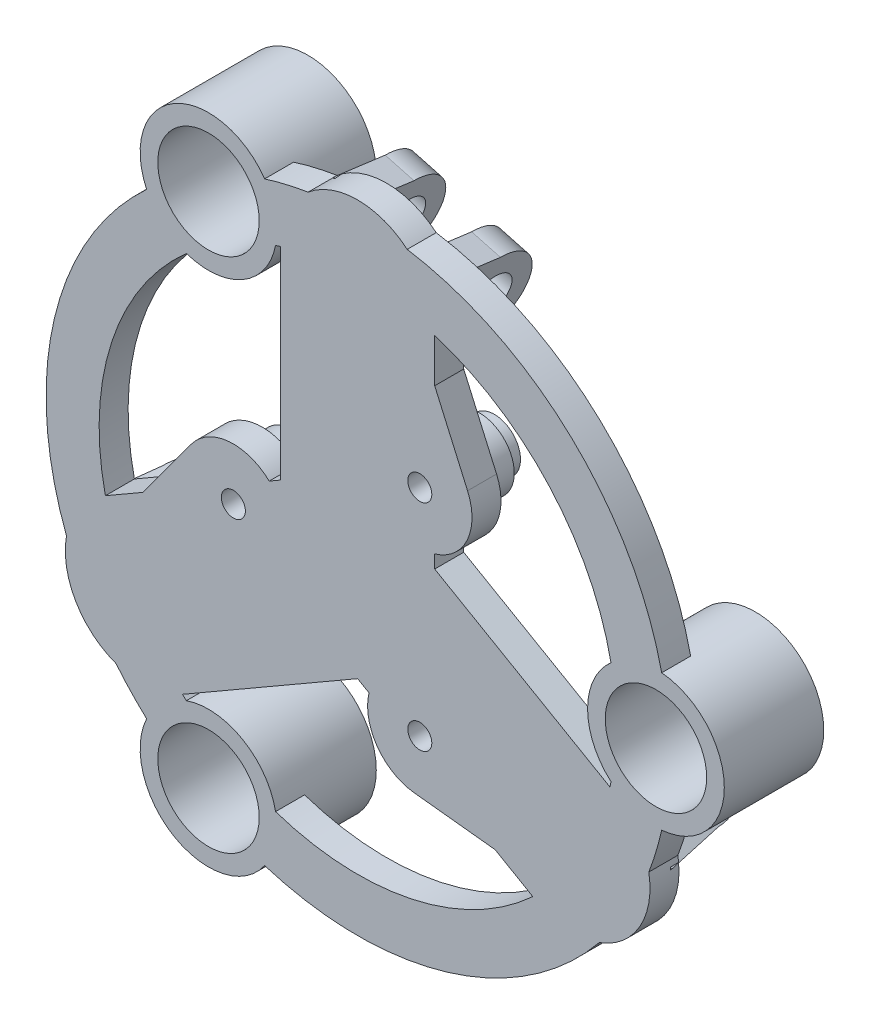
SolidWorks part; units mm, degrees
ref_plane "Front Plane" through (0, 0, 0) normal (0, 0, 1) x (1, 0, 0)
ref_plane "Top Plane" through (0, 0, 0) normal (0, 1, 0) x (1, 0, 0)
ref_plane "Right Plane" through (0, 0, 0) normal (1, 0, 0) x (0, 0, -1)
sketch "S01 - Joining centre of floating Y" plane through (0, 0, 0) normal (0, 0, 1) x (1, 0, 0)
  circle A0 centre (0, 0) radius 9
  dimension "D1" = 18
extrude "01 - Joining centre of floating Y" add sketch "S01 - Joining centre of floating Y" along normal blind 3.5 from offset 33.5
sketch "S02 - Floating spoke 1" plane through (0, 0, 0) normal (0, 0, 1) x (1, 0, 0)
  line L0 (4.65, -8.054) -> (-21.3308, -23.054)
  line L1 (-30.6308, -6.946) -> (-4.65, 8.054)
  arc A0 (-21.3308, -23.054) -> (-30.6308, -6.946) centre (-25.9808, -15) cw
  arc A1 (-4.65, 8.054) -> (4.65, -8.054) centre (0, 0) cw
  dimension "D1" = 9.3
  dimension "D2" = 9.3
  dimension "D3" = 4.65
  dimension "D4" = 4.65
  dimension "D5" = 21.3308
  dimension "D6" = 25.9808
  dimension "D7" = 30.6308
  dimension "D8" = 6.946
extrude "02 - Floating spoke 1" add sketch "S02 - Floating spoke 1" along normal blind 3.5 from offset 33.5
sketch "S03 - Floating spoke 2" plane through (0, 0, 0) normal (0, 0, 1) x (1, 0, 0)
  line L0 (4.65, 8.054) -> (30.6308, -6.946)
  line L1 (21.3308, -23.054) -> (-4.65, -8.054)
  arc A0 (30.6308, -6.946) -> (21.3308, -23.054) centre (25.9808, -15) cw
  arc A1 (-4.65, -8.054) -> (4.65, 8.054) centre (0, 0) cw
  dimension "D1" = 9.3
  dimension "D2" = 9.3
  dimension "D3" = 4.65
  dimension "D4" = 21.3308
  dimension "D5" = 25.9808
  dimension "D6" = 30.6308
  dimension "D7" = 4.65
  dimension "D8" = 6.946
extrude "03 - Floating spoke 2" add sketch "S03 - Floating spoke 2" along normal blind 3.5 from offset 33.5
sketch "S04 - Floating spoke 3" plane through (0, 0, 0) normal (0, 0, 1) x (1, 0, 0)
  line L0 (-9.3, 0) -> (-9.3, 30)
  line L1 (9.3, 30) -> (9.3, 0)
  arc A0 (-9.3, 30) -> (9.3, 30) centre (0, 30) cw
  arc A1 (9.3, 0) -> (-9.3, 0) centre (0, 0) cw
  dimension "D1" = 9.3
  dimension "D2" = 30
extrude "04 - Floating spoke 3" add sketch "S04 - Floating spoke 3" along normal blind 3.5 from offset 33.5
sketch "S05 - Moving tendon tie web 1" plane through (0, 0, 0) normal (0, 0, 1) x (1, 0, 0)
  line L0 (25.2997, -21.2631) -> (6.8189, -19.2535)
  line L1 (8.1811, -6.7273) -> (26.6618, -8.7369)
  arc A0 (6.8189, -19.2535) -> (8.1811, -6.7273) centre (7.5, -12.9904) cw
  arc A1 (26.6618, -8.7369) -> (25.2997, -21.2631) centre (25.9808, -15) cw
  dimension "D1" = 6.3
  dimension "D2" = 6.3
  dimension "D3" = 6.8189
  dimension "D4" = 7.5
  dimension "D5" = 8.1811
  dimension "D6" = 25.2997
  dimension "D7" = 25.9808
  dimension "D8" = 26.6618
  dimension "D9" = 6.7273
  dimension "D10" = 8.7369
extrude "05 - Moving tendon tie web 1" add sketch "S05 - Moving tendon tie web 1" along normal blind 3.5 from offset 33.5
sketch "S06 - Tendon anchor base 1" plane through (0, 0, 0) normal (0, 0, 1) x (1, 0, 0)
  circle A0 centre (7.5, -12.9904) radius 4.2
  dimension "D1" = 8.4
  dimension "D2" = 7.5
  dimension "D3" = 12.9904
extrude "06 - Tendon anchor base 1" add sketch "S06 - Tendon anchor base 1" along normal blind 3.7 from offset 29.8
sketch "S07 - Tendon mouth 1" plane through (0, 0, 0) normal (0, 0, 1) x (1, 0, 0)
  circle A0 centre (7.5, -12.9904) radius 3.15
  dimension "D1" = 6.3
  dimension "D2" = 7.5
  dimension "D3" = 12.9904
extrude "07 - Tendon mouth 1" add sketch "S07 - Tendon mouth 1" along normal blind 1.8 from offset 28
sketch "S08 - Moving tendon tie web 2" plane through (0, 0, 0) normal (0, 0, 1) x (1, 0, 0)
  line L0 (5.7645, 32.5417) -> (13.2645, 15.5321)
  line L1 (1.7355, 10.4487) -> (-5.7645, 27.4583)
  arc A0 (13.2645, 15.5321) -> (1.7355, 10.4487) centre (7.5, 12.9904) cw
  arc A1 (-5.7645, 27.4583) -> (5.7645, 32.5417) centre (0, 30) cw
  dimension "D1" = 6.3
  dimension "D2" = 6.3
  dimension "D3" = 1.7355
  dimension "D4" = 5.7645
  dimension "D5" = 7.5
  dimension "D6" = 13.2645
  dimension "D7" = 5.7645
  dimension "D8" = 10.4487
  dimension "D9" = 27.4583
extrude "08 - Moving tendon tie web 2" add sketch "S08 - Moving tendon tie web 2" along normal blind 3.5 from offset 33.5
sketch "S09 - Tendon anchor base 2" plane through (0, 0, 0) normal (0, 0, 1) x (1, 0, 0)
  circle A0 centre (7.5, 12.9904) radius 4.2
  dimension "D1" = 8.4
  dimension "D2" = 7.5
  dimension "D3" = 12.9904
extrude "09 - Tendon anchor base 2" add sketch "S09 - Tendon anchor base 2" along normal blind 3.7 from offset 29.8
sketch "S10 - Tendon mouth 2" plane through (0, 0, 0) normal (0, 0, 1) x (1, 0, 0)
  circle A0 centre (7.5, 12.9904) radius 3.15
  dimension "D1" = 6.3
  dimension "D2" = 7.5
  dimension "D3" = 12.9904
extrude "10 - Tendon mouth 2" add sketch "S10 - Tendon mouth 2" along normal blind 1.8 from offset 28
sketch "S11 - Moving tendon tie web 3" plane through (0, 0, 0) normal (0, 0, 1) x (1, 0, 0)
  line L0 (-31.0642, -11.2786) -> (-20.0835, 3.7214)
  line L1 (-9.9165, -3.7214) -> (-20.8973, -18.7214)
  arc A0 (-20.0835, 3.7214) -> (-9.9165, -3.7214) centre (-15, 0) cw
  arc A1 (-20.8973, -18.7214) -> (-31.0642, -11.2786) centre (-25.9808, -15) cw
  dimension "D1" = 6.3
  dimension "D2" = 6.3
  dimension "D3" = 9.9165
  dimension "D4" = 15
  dimension "D5" = 20.0835
  dimension "D6" = 20.8973
  dimension "D7" = 25.9808
  dimension "D8" = 31.0642
  dimension "D9" = 11.2786
extrude "11 - Moving tendon tie web 3" add sketch "S11 - Moving tendon tie web 3" along normal blind 3.5 from offset 33.5
sketch "S12 - Tendon anchor base 3" plane through (0, 0, 0) normal (0, 0, 1) x (1, 0, 0)
  circle A0 centre (-15, 0) radius 4.2
  dimension "D1" = 8.4
  dimension "D2" = 15
extrude "12 - Tendon anchor base 3" add sketch "S12 - Tendon anchor base 3" along normal blind 3.7 from offset 29.8
sketch "S13 - Tendon mouth 3" plane through (0, 0, 0) normal (0, 0, 1) x (1, 0, 0)
  circle A0 centre (-15, 0) radius 3.15
  dimension "D1" = 6.3
  dimension "D2" = 15
extrude "13 - Tendon mouth 3" add sketch "S13 - Tendon mouth 3" along normal blind 1.8 from offset 28
sketch "S14 - Joined drive hoop" plane through (0, 0, 0) normal (0, 0, 1) x (1, 0, 0)
  circle A0 centre (0, 0) radius 37.6
  circle A1 centre (0, 0) radius 31.2
  dimension "D1" = 62.4
  dimension "D2" = 75.2
extrude "14 - Joined drive hoop" add sketch "S14 - Joined drive hoop" along normal blind 3.5 from offset 33.5
sketch "S15 - Sliding guide barrel 1" plane through (0, 0, 0) normal (0, 0, 1) x (1, 0, 0)
  circle A0 centre (36, 0) radius 8.25
  dimension "D1" = 16.5
  dimension "D2" = 36
extrude "15 - Sliding guide barrel 1" add sketch "S15 - Sliding guide barrel 1" along normal blind 12 from offset 25
sketch "S16 - Sliding guide barrel 2" plane through (0, 0, 0) normal (0, 0, 1) x (1, 0, 0)
  circle A0 centre (-18, 31.1769) radius 8.25
  dimension "D1" = 16.5
  dimension "D2" = 18
  dimension "D3" = 31.1769
extrude "16 - Sliding guide barrel 2" add sketch "S16 - Sliding guide barrel 2" along normal blind 12 from offset 25
sketch "S17 - Sliding guide barrel 3" plane through (0, 0, 0) normal (0, 0, 1) x (1, 0, 0)
  circle A0 centre (-18, -31.1769) radius 8.25
  dimension "D1" = 16.5
  dimension "D2" = 18
  dimension "D3" = 31.1769
extrude "17 - Sliding guide barrel 3" add sketch "S17 - Sliding guide barrel 3" along normal blind 12 from offset 25
sketch "S18 - Guide bushing seats" plane through (0, 0, 0) normal (0, 0, 1) x (1, 0, 0)
  circle A0 centre (36, 0) radius 6.12
  circle A1 centre (-18, 31.1769) radius 6.12
  circle A2 centre (-18, -31.1769) radius 6.12
  dimension "D1" = 12.24
  dimension "D2" = 12.24
  dimension "D3" = 12.24
  dimension "D4" = 36
  dimension "D5" = 18
  dimension "D6" = 31.1769
  dimension "D7" = 31.1769
extrude "18 - Guide bushing seats" cut sketch "S18 - Guide bushing seats" along normal blind 14 from offset 24
sketch "S19 - Through tendon tie eyes" plane through (0, 0, 0) normal (0, 0, 1) x (1, 0, 0)
  circle A0 centre (7.5, -12.9904) radius 1.45
  circle A1 centre (7.5, 12.9904) radius 1.45
  circle A2 centre (-15, 0) radius 1.45
  dimension "D1" = 2.9
  dimension "D2" = 2.9
  dimension "D3" = 2.9
  dimension "D4" = 7.5
  dimension "D5" = 15
  dimension "D6" = 12.9904
  dimension "D7" = 12.9904
extrude "19 - Through tendon tie eyes" cut sketch "S19 - Through tendon tie eyes" along normal blind 10 from offset 27.8
sketch3d "Plane points - Integral B1 fork cheek L"
  point P0 (-25.9808, -15, 28)
  point P1 (-8.5941, -10.3413, 28)
  point P2 (-25.9808, -15, 10)
ref_plane "Drilling plane - Integral B1 fork cheek L" through (2.0096, -7.5, 0) normal (-0.2588, 0.9659, 0) x (0.9659, 0.2588, 0)
sketch "S20 - Integral B1 fork cheek L" plane through (2.0096, -7.5, 0) normal (-0.2588, 0.9659, 0) x (0.9659, 0.2588, 0)
  line L0 (-35.0778, -34.5) -> (-22.8778, -34.5)
  line L1 (-22.8778, -34.5) -> (-24.0278, -28)
  line L2 (-33.9278, -28) -> (-35.0778, -34.5)
  arc A0 (-24.0278, -28) -> (-33.9278, -28) centre (-28.9778, -28) ccw
  dimension "D1" = 4.95
  dimension "D2" = 22.8778
  dimension "D3" = 28.9778
  dimension "D4" = 35.0778
  dimension "D5" = 28
  dimension "D6" = 34.5
extrude "20 - Integral B1 fork cheek L" add sketch "S20 - Integral B1 fork cheek L" along normal blind 3.6 from offset 7.2 offset against normal yes
sketch3d "Plane points - Integral B1 fork cheek R"
  point P0 (-25.9808, -15, 28)
  point P1 (-8.5941, -10.3413, 28)
  point P2 (-25.9808, -15, 10)
ref_plane "Drilling plane - Integral B1 fork cheek R" through (2.0096, -7.5, 0) normal (-0.2588, 0.9659, 0) x (0.9659, 0.2588, 0)
sketch "S21 - Integral B1 fork cheek R" plane through (2.0096, -7.5, 0) normal (-0.2588, 0.9659, 0) x (0.9659, 0.2588, 0)
  line L0 (-35.0778, -34.5) -> (-22.8778, -34.5)
  line L1 (-22.8778, -34.5) -> (-24.0278, -28)
  line L2 (-33.9278, -28) -> (-35.0778, -34.5)
  arc A0 (-24.0278, -28) -> (-33.9278, -28) centre (-28.9778, -28) ccw
  dimension "D1" = 4.95
  dimension "D2" = 22.8778
  dimension "D3" = 28.9778
  dimension "D4" = 35.0778
  dimension "D5" = 28
  dimension "D6" = 34.5
extrude "21 - Integral B1 fork cheek R" add sketch "S21 - Integral B1 fork cheek R" along normal blind 3.6 from offset 3.6
sketch3d "Plane points - B1 pivot through both cheeks"
  point P0 (-25.9808, -15, 28)
  point P1 (-8.5941, -10.3413, 28)
  point P2 (-25.9808, -15, 10)
ref_plane "Drilling plane - B1 pivot through both cheeks" through (2.0096, -7.5, 0) normal (-0.2588, 0.9659, 0) x (0.9659, 0.2588, 0)
sketch "S22 - B1 pivot through both cheeks" plane through (2.0096, -7.5, 0) normal (-0.2588, 0.9659, 0) x (0.9659, 0.2588, 0)
  circle A0 centre (-28.9778, -28) radius 1.65
  dimension "D1" = 3.3
  dimension "D2" = 28.9778
  dimension "D3" = 28
extrude "22 - B1 pivot through both cheeks" cut sketch "S22 - B1 pivot through both cheeks" along normal blind 15 from offset 7.5 offset against normal yes
sketch3d "Plane points - B1 recessed pivot screw head"
  point P0 (-25.9808, -15, 28)
  point P1 (-8.5941, -10.3413, 28)
  point P2 (-25.9808, -15, 10)
ref_plane "Drilling plane - B1 recessed pivot screw head" through (2.0096, -7.5, 0) normal (-0.2588, 0.9659, 0) x (0.9659, 0.2588, 0)
sketch "S23 - B1 recessed pivot screw head" plane through (2.0096, -7.5, 0) normal (-0.2588, 0.9659, 0) x (0.9659, 0.2588, 0)
  circle A0 centre (-28.9778, -28) radius 2.7
  dimension "D1" = 5.4
  dimension "D2" = 28.9778
  dimension "D3" = 28
extrude "23 - B1 recessed pivot screw head" cut sketch "S23 - B1 recessed pivot screw head" along normal blind 1.5 from offset 7.3 offset against normal yes
sketch3d "Plane points - Integral B2 fork cheek L"
  point P0 (25.9808, -15, 28)
  point P1 (13.2528, -2.2721, 28)
  point P2 (25.9808, -15, 10)
ref_plane "Drilling plane - Integral B2 fork cheek L" through (5.4904, 5.4904, 0) normal (-0.7071, -0.7071, 0) x (0, 0, 1)
sketch "S24 - Integral B2 fork cheek L" plane through (5.4904, 5.4904, 0) normal (-0.7071, -0.7071, 0) x (0, 0, 1)
  line L0 (34.5, -35.0778) -> (34.5, -22.8778)
  line L1 (34.5, -22.8778) -> (28, -24.0278)
  line L2 (28, -33.9278) -> (34.5, -35.0778)
  arc A0 (28, -24.0278) -> (28, -33.9278) centre (28, -28.9778) ccw
  dimension "D1" = 4.95
  dimension "D2" = 28
  dimension "D3" = 34.5
  dimension "D4" = 22.8778
  dimension "D5" = 28.9778
  dimension "D6" = 35.0778
extrude "24 - Integral B2 fork cheek L" add sketch "S24 - Integral B2 fork cheek L" along normal blind 3.6 from offset 7.2 offset against normal yes
sketch3d "Plane points - Integral B2 fork cheek R"
  point P0 (25.9808, -15, 28)
  point P1 (13.2528, -2.2721, 28)
  point P2 (25.9808, -15, 10)
ref_plane "Drilling plane - Integral B2 fork cheek R" through (5.4904, 5.4904, 0) normal (-0.7071, -0.7071, 0) x (0, 0, 1)
sketch "S25 - Integral B2 fork cheek R" plane through (5.4904, 5.4904, 0) normal (-0.7071, -0.7071, 0) x (0, 0, 1)
  line L0 (34.5, -35.0778) -> (34.5, -22.8778)
  line L1 (34.5, -22.8778) -> (28, -24.0278)
  line L2 (28, -33.9278) -> (34.5, -35.0778)
  arc A0 (28, -24.0278) -> (28, -33.9278) centre (28, -28.9778) ccw
  dimension "D1" = 4.95
  dimension "D2" = 28
  dimension "D3" = 34.5
  dimension "D4" = 22.8778
  dimension "D5" = 28.9778
  dimension "D6" = 35.0778
extrude "25 - Integral B2 fork cheek R" add sketch "S25 - Integral B2 fork cheek R" along normal blind 3.6 from offset 3.6
sketch3d "Plane points - B2 pivot through both cheeks"
  point P0 (25.9808, -15, 28)
  point P1 (13.2528, -2.2721, 28)
  point P2 (25.9808, -15, 10)
ref_plane "Drilling plane - B2 pivot through both cheeks" through (5.4904, 5.4904, 0) normal (-0.7071, -0.7071, 0) x (0, 0, 1)
sketch "S26 - B2 pivot through both cheeks" plane through (5.4904, 5.4904, 0) normal (-0.7071, -0.7071, 0) x (0, 0, 1)
  circle A0 centre (28, -28.9778) radius 2.6
  dimension "D1" = 5.2
  dimension "D2" = 28
  dimension "D3" = 28.9778
extrude "26 - B2 pivot through both cheeks" cut sketch "S26 - B2 pivot through both cheeks" along normal blind 15 from offset 7.5 offset against normal yes
sketch3d "Plane points - B2 recessed pivot screw head"
  point P0 (25.9808, -15, 28)
  point P1 (13.2528, -2.2721, 28)
  point P2 (25.9808, -15, 10)
ref_plane "Drilling plane - B2 recessed pivot screw head" through (5.4904, 5.4904, 0) normal (-0.7071, -0.7071, 0) x (0, 0, 1)
sketch "S27 - B2 recessed pivot screw head" plane through (5.4904, 5.4904, 0) normal (-0.7071, -0.7071, 0) x (0, 0, 1)
  circle A0 centre (28, -28.9778) radius 2.7
  dimension "D1" = 5.4
  dimension "D2" = 28
  dimension "D3" = 28.9778
extrude "27 - B2 recessed pivot screw head" cut sketch "S27 - B2 recessed pivot screw head" along normal blind 1.5 from offset 7.3 offset against normal yes
sketch3d "Plane points - Integral B3 fork cheek L"
  point P0 (0, 30, 28)
  point P1 (-4.6587, 12.6133, 28)
  point P2 (0, 30, 10)
ref_plane "Drilling plane - Integral B3 fork cheek L" through (-7.5, 2.0096, 0) normal (0.9659, -0.2588, 0) x (0, 0, -1)
sketch "S28 - Integral B3 fork cheek L" plane through (-7.5, 2.0096, 0) normal (0.9659, -0.2588, 0) x (0, 0, -1)
  line L0 (-34.5, 35.0778) -> (-34.5, 22.8778)
  line L1 (-34.5, 22.8778) -> (-28, 24.0278)
  line L2 (-28, 33.9278) -> (-34.5, 35.0778)
  arc A0 (-28, 24.0278) -> (-28, 33.9278) centre (-28, 28.9778) ccw
  dimension "D1" = 4.95
  dimension "D2" = 28
  dimension "D3" = 34.5
  dimension "D4" = 22.8778
  dimension "D5" = 28.9778
  dimension "D6" = 35.0778
extrude "28 - Integral B3 fork cheek L" add sketch "S28 - Integral B3 fork cheek L" along normal blind 3.6 from offset 7.2 offset against normal yes
sketch3d "Plane points - Integral B3 fork cheek R"
  point P0 (0, 30, 28)
  point P1 (-4.6587, 12.6133, 28)
  point P2 (0, 30, 10)
ref_plane "Drilling plane - Integral B3 fork cheek R" through (-7.5, 2.0096, 0) normal (0.9659, -0.2588, 0) x (0, 0, -1)
sketch "S29 - Integral B3 fork cheek R" plane through (-7.5, 2.0096, 0) normal (0.9659, -0.2588, 0) x (0, 0, -1)
  line L0 (-34.5, 35.0778) -> (-34.5, 22.8778)
  line L1 (-34.5, 22.8778) -> (-28, 24.0278)
  line L2 (-28, 33.9278) -> (-34.5, 35.0778)
  arc A0 (-28, 24.0278) -> (-28, 33.9278) centre (-28, 28.9778) ccw
  dimension "D1" = 4.95
  dimension "D2" = 28
  dimension "D3" = 34.5
  dimension "D4" = 22.8778
  dimension "D5" = 28.9778
  dimension "D6" = 35.0778
extrude "29 - Integral B3 fork cheek R" add sketch "S29 - Integral B3 fork cheek R" along normal blind 3.6 from offset 3.6
sketch3d "Plane points - B3 pivot through both cheeks"
  point P0 (0, 30, 28)
  point P1 (-4.6587, 12.6133, 28)
  point P2 (0, 30, 10)
ref_plane "Drilling plane - B3 pivot through both cheeks" through (-7.5, 2.0096, 0) normal (0.9659, -0.2588, 0) x (0, 0, -1)
sketch "S30 - B3 pivot through both cheeks" plane through (-7.5, 2.0096, 0) normal (0.9659, -0.2588, 0) x (0, 0, -1)
  circle A0 centre (-28, 28.9778) radius 2.6
  dimension "D1" = 5.2
  dimension "D2" = 28
  dimension "D3" = 28.9778
extrude "30 - B3 pivot through both cheeks" cut sketch "S30 - B3 pivot through both cheeks" along normal blind 15 from offset 7.5 offset against normal yes
sketch3d "Plane points - B3 recessed pivot screw head"
  point P0 (0, 30, 28)
  point P1 (-4.6587, 12.6133, 28)
  point P2 (0, 30, 10)
ref_plane "Drilling plane - B3 recessed pivot screw head" through (-7.5, 2.0096, 0) normal (0.9659, -0.2588, 0) x (0, 0, -1)
sketch "S31 - B3 recessed pivot screw head" plane through (-7.5, 2.0096, 0) normal (0.9659, -0.2588, 0) x (0, 0, -1)
  circle A0 centre (-28, 28.9778) radius 2.7
  dimension "D1" = 5.4
  dimension "D2" = 28
  dimension "D3" = 28.9778
extrude "31 - B3 recessed pivot screw head" cut sketch "S31 - B3 recessed pivot screw head" along normal blind 1.5 from offset 7.3 offset against normal yes
sketch "Sketch1" plane through (0.1461, -0.5453, 0) normal (-0.2588, 0.9659, 0) x (0.9659, 0.2588, 0)
  circle A0 centre (-28.9778, -28) radius 2.6
  dimension "D1" = 5.2
extrude "Cut-Extrude1" cut sketch "Sketch1" against normal blind 16 and the other way through all
